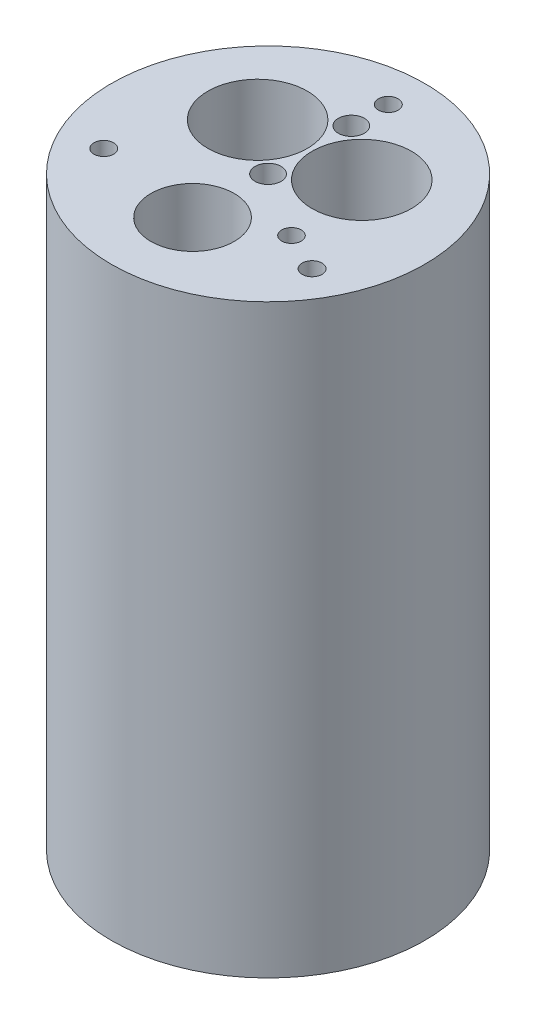
SolidWorks part; units mm, degrees
material "PLA"
ref_plane "Front Plane" through (0, 0, 0) normal (0, 0, 1) x (1, 0, 0)
ref_plane "Top Plane" through (0, 0, 0) normal (0, 1, 0) x (1, 0, 0)
ref_plane "Right Plane" through (0, 0, 0) normal (1, 0, 0) x (0, 0, -1)
sketch "Sketch1" plane through (0, 0, 0) normal (0, 1, 0) x (1, 0, 0)
  circle A0 centre (0, 0) radius 38.227
  dimension "D1" = 76.454
extrude "Boss-Extrude1" add sketch "Sketch1" along normal blind 142.8496
sketch "Sketch2" plane through (0, 142.8496, 0) normal (0, 1, 0) x (1, 0, 0)
  circle A0 centre (0, 29.337) radius 2.413
  circle A3 centre (0, 0) radius 29.464 construction
  circle A4 centre (25.4066, -14.6685) radius 2.413
  circle A5 centre (-25.4066, -14.6685) radius 2.413
  point P11 (0, 0)
  dimension "D2" = 4.826
  dimension "D4" = 58.928
  dimension "D1" = 29.337
extrude "Cut-Extrude1" cut sketch "Sketch2" against normal through all
sketch "Sketch3" plane through (0, 142.8496, 0) normal (0, 1, 0) x (1, 0, 0)
  line L0 (-12.7, 10.16) -> (12.7, 10.16) construction
  circle A1 centre (-12.7, 10.16) radius 12.1285
  circle A3 centre (0, 29.337) radius 2.413 construction
  circle A6 centre (0, 29.337) radius 2.413 construction
  circle A8 centre (12.7, 10.16) radius 12.1285
  point P13 (0, 10.16)
  dimension "D1" = 24.257
  dimension "D2" = 24.257
  dimension "D3" = 25.4
  dimension "D4" = 10.16
extrude "Cut-Extrude2" cut sketch "Sketch3" against normal through all
ref_axis "Axis1" through (0, -7.1425, 0) along (0, 1, 0)
ref_plane "Plane1" through (0, 71.4248, 0) normal (0, -1, 0) x (-1, 0, 0)
sketch "Sketch4" plane through (0, 142.8496, 0) normal (0, 1, 0) x (1, 0, 0)
  line L0 (-12.7, 10.16) -> (12.7, 10.16) construction
  circle A0 centre (0, 20.32) radius 3.175
  circle A1 centre (0, 0) radius 3.175
  circle A2 centre (12.7, 10.16) radius 12.1285 construction
  circle A3 centre (-12.7, 10.16) radius 12.1285 construction
  circle A4 centre (12.7, 10.16) radius 12.1285 construction
  circle A5 centre (-12.7, 10.16) radius 12.1285 construction
  dimension "D1" = 6.35
  dimension "D2" = 6.35
  dimension "D3" = 10.16
  dimension "D4" = 10.16
extrude "Cut-Extrude3" cut sketch "Sketch4" against normal blind 6.35
sketch "Sketch5" plane through (0, 142.8496, 0) normal (0, 1, 0) x (1, 0, 0)
  circle A0 centre (0, -18.415) radius 4.1275 construction
  circle A1 centre (0, -18.415) radius 10.16
  dimension "D1" = 20.32
  dimension "D2" = 8.255
  dimension "D3" = 18.415
extrude "Cut-Extrude4" cut sketch "Sketch5" against normal blind 17.78
sketch "Sketch6" plane through (0, 142.8496, 0) normal (0, 1, 0) x (1, 0, 0)
  line L0 (-15.875, -10.16) -> (15.875, -10.16) construction
  line L1 (0, 0) -> (0, -10.16) construction
  circle A0 centre (15.875, -10.16) radius 2.3813
  circle A1 centre (-15.875, -10.16) radius 2.3813
  dimension "D1" = 4.7625
  dimension "D2" = 4.7625
  dimension "D3" = 10.16
  dimension "D4" = 31.75
extrude "Cut-Extrude5" cut sketch "Sketch6" against normal through all both and the other way through all contours A0
equation "\"D1@Sketch1\"=3.01-\"tolerance_body_tube\"+0.04-0.02"
equation "\"tolerance_body_tube\"= 0.02"
equation "\"tolerance_threaded_rods\"= 0.02"
equation "\"tolerance_peregrines\"= 0.04"
equation "\"D1@Sketch3\"=\"D2@Sketch3\""
equation "\"D2@Sketch3\"=0.935+\"tolerance_peregrines\"-0.02"
equation "\"D2@Sketch2\"=0.170+\"tolerance_threaded_rods\""
